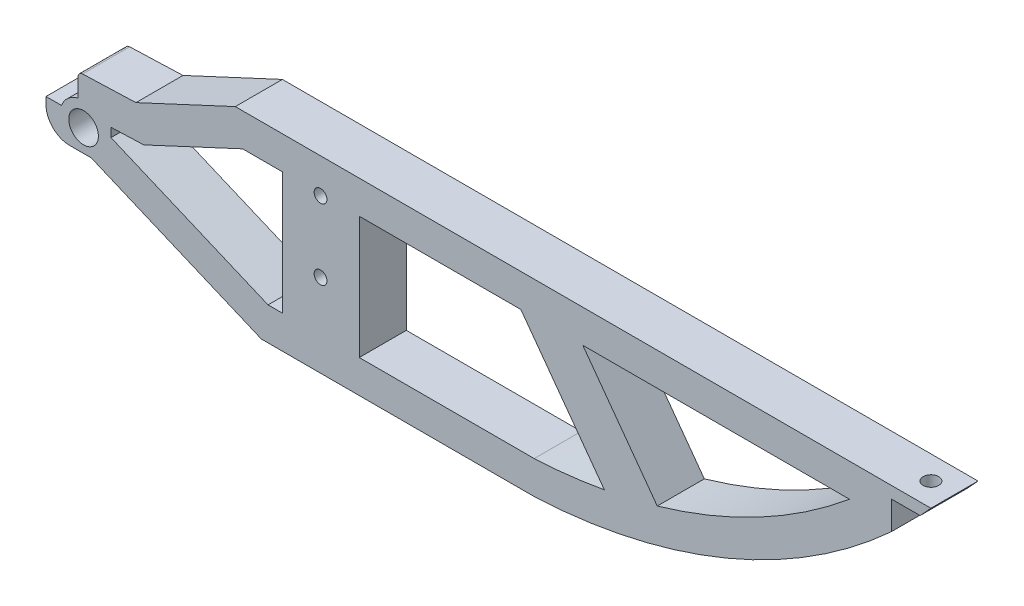
SolidWorks part; units mm, degrees
ref_plane "Front Plane" through (0, 0, 0) normal (0, 0, 1) x (1, 0, 0)
ref_plane "Top Plane" through (0, 0, 0) normal (0, 1, 0) x (1, 0, 0)
ref_plane "Right Plane" through (0, 0, 0) normal (1, 0, 0) x (0, 0, -1)
sketch "Sketch1" plane through (0, 0, 0) normal (0, 0, 1) x (1, 0, 0)
  line L1 (120.65, 25.4) -> (-120.65, 25.4)
  line L2 (120.65, 25.4) -> (120.65, -25.4)
  line L3 (120.65, -25.4) -> (-120.65, -25.4)
  line L4 (-120.65, 25.4) -> (-120.65, -25.4)
  line L5 (120.65, 25.4) -> (-120.65, -25.4) construction
  line L6 (120.65, -25.4) -> (-120.65, 25.4) construction
  point P0 (0, 0)
  dimension "D1" = 241.3
  dimension "D2" = 50.8
extrude "Boss-Extrude1" add sketch "Sketch1" along normal blind 12.7
sketch "Sketch3" plane through (0, 0, 12.7) normal (0, 0, 1) x (1, 0, 0)
  line L0 (0, 0) -> (-120.65, 0) construction
  line L1 (-120.65, 25.4) -> (-120.65, -25.4) construction
  circle A0 centre (-107.95, 0) radius 4
  dimension "D2" = 8
  dimension "D1" = 12.7
extrude "Cut-Extrude1" cut sketch "Sketch3" against normal through all
sketch "Sketch5" plane through (0, 0, 12.7) normal (0, 0, 1) x (1, 0, 0)
  line L0 (-120.65, -25.4) -> (120.65, -25.4) construction
  line L1 (-105.8942, -6.008) -> (-59.9903, -25.4)
  line L2 (-107.95, 6.35) -> (-67.0151, 25.4)
  line L3 (120.65, 25.4) -> (-120.65, 25.4) construction
  line L4 (-67.0151, 25.4) -> (-120.65, 25.4)
  line L5 (-120.65, 25.4) -> (-120.65, -25.4)
  line L6 (-120.65, -25.4) -> (-59.9903, -25.4)
  line L7 (120.65, 25.4) -> (120.65, -25.4)
  line L8 (120.65, -25.4) -> (0, -25.4)
  line L9 (-109.9582, -6.0241) -> (-105.8942, -6.008)
  line L10 (-118.0862, -6.0241) -> (-109.9582, -6.0241)
  line L11 (-118.0862, -6.0241) -> (-118.0862, 2.2309)
  line L12 (-118.0862, 2.2309) -> (-113.8952, 2.2309)
  arc A0 (0, -25.4) -> (120.65, 25.4) centre (6.9175, 126.8429) ccw
  arc A1 (-109.9582, -6.0241) -> (-105.8942, -6.008) centre (-107.95, 0) ccw construction
  arc A2 (-107.95, 6.35) -> (-113.8952, 2.2309) centre (-107.95, 0) ccw
  point P15 (-116.1445, -2.9908)
  line M3 (-120.65, 25.4) -> (-120.65, -25.4)
  line M4 (-120.65, -25.4) -> (120.65, -25.4)
  line M5 (120.65, -25.4) -> (120.65, 25.4)
  line M6 (120.65, 25.4) -> (-120.65, 25.4)
  dimension "D1" = 152.4
  dimension "D2" = 12.7
  dimension "D3" = 45.1505
  dimension "D4" = 45.9039
  dimension "D5" = 8.255
  dimension "D6" = 4.191
  dimension "D7" = 8.128
extrude "Cut-Extrude2" cut sketch "Sketch5" against normal through all contours A2 L2 L1 M6 M3 M4 | A0 L8 M5 region at (-83.2502, -16.4329, 12.7) region at (93.5193, -10.6939, 12.7)
sketch "Sketch6" plane through (0, 0, 12.7) normal (0, 0, 1) x (1, 0, 0)
  line L0 (-107.95, 0) -> (91.396, 0) construction
  arc A0 (13.8349, -25.4) -> (120.65, 25.4) centre (6.9175, 126.8429) ccw construction
  circle A1 centre (19.05, 0) radius 3.1347
  dimension "D1" = 127
sketch "Sketch7" plane through (0, 0, 0) normal (0, 0, -1) x (-1, 0, 0)
  line L0 (44.0204, -2.9977) -> (44.0204, 16.0523) construction
  point P3 (44.0204, -2.9977)
  point P4 (44.0204, 16.0523)
  dimension "D1" = 19.05
sketch "Sketch8" plane through (0, 0, 0) normal (0, 0, -1) x (-1, 0, 0)
  point P0 (44.0204, 16.0523)
  point P3 (44.0204, -2.9977)
hole_wizard "Tap Drill for #8-32 Tap1" positions "Sketch8" profile "Sketch9" hole size "#8-32" standard "ANSI Inch" end condition through all
sketch "Sketch9" plane through (-44.0204, 16.0523, 0) normal (1, 0, 0) x (0, 1, 0)
  line L0 (0, 0) -> (0, 12.7)
  line L1 (0, 12.7) -> (1.7272, 12.7)
  line L2 (1.7272, 12.7) -> (1.7272, 0)
  line L5 (1.7272, 0) -> (0, 0)
  line L11 (0, -6.35) -> (0, 107.95) construction
  dimension "Thru Hole Dia." = 3.4544
  dimension "Thru Hole Depth" = 12.7
ref_plane "Plane1" through (-114.3, 0, 0) normal (-1, 0, 0) x (0, 0, 1)
sketch "Sketch10" plane through (-114.3, 0, 0) normal (-1, 0, 0) x (0, 0, 1)
  line L0 (0, 0) -> (12.7, 0) construction
  line L1 (12.7, -3.1347) -> (12.7, 3.1347) construction
  circle A0 centre (6.0894, 0) radius 1.905
  dimension "D1" = 3.81
extrude "Cut-Extrude3" cut sketch "Sketch10" against normal blind 5.08
sketch "Sketch11" plane through (0, 0, 12.7) normal (0, 0, 1) x (1, 0, 0)
  line L0 (-93.8249, 12.9234) -> (-109.4459, 12.9234) construction
  line L1 (-107.95, 6.35) -> (-67.0151, 25.4) construction
  line L2 (-109.4459, 12.9234) -> (-109.4459, 5.6538) construction
  line L3 (-93.8249, 12.9234) -> (-109.4459, 5.6538)
  line L4 (-93.8249, 12.9234) -> (-109.4459, 12.3779)
  line L5 (-109.4459, 12.3779) -> (-109.4459, 5.6538)
  circle A1 centre (-107.95, 0) radius 4 construction
  dimension "D1" = 15.621
  dimension "D2" = 5.6538
  dimension "D3" = 178
extrude "Boss-Extrude2" add sketch "Sketch11" against normal up to surface (12.7 mm away) up to face at (-45.7476, 16.0523, 0)
sketch "Sketch12" plane through (0, 0, 12.7) normal (0, 0, 1) x (1, 0, 0)
  line L1 (10.0217, 16.51) -> (-33.5733, 16.51)
  line L24 (-33.5733, 16.51) -> (-33.5733, -16.51)
  line L25 (-54.2244, 16.51) -> (-54.2244, -16.51)
  line L26 (-54.2244, 16.51) -> (-65.0478, 16.51)
  line L27 (-33.5733, -16.51) -> (13.63, -16.51)
  line L28 (10.0217, 16.51) -> (32.5572, -14.3581)
  line L29 (26.7339, 16.51) -> (46.8231, -11.0072)
  line L30 (-100.5559, 3.793) -> (-100.5559, 1.3876)
  line L31 (-100.5559, 1.3876) -> (-58.1896, -16.51)
  line L32 (-58.1896, -16.51) -> (13.63, -16.51)
  line L33 (98.6876, 16.51) -> (-65.0478, 16.51)
  line L34 (-65.0478, 16.51) -> (-91.7106, 4.1018)
  line L35 (-91.7106, 4.1018) -> (-100.5559, 3.793)
  line L36 (-100.5559, 3.793) -> (-100.5559, 1.3876)
  line L37 (-100.5559, 1.3876) -> (-58.1896, -16.51)
  line L38 (-58.1896, -16.51) -> (-54.2244, -16.51)
  line L39 (98.6876, 16.51) -> (26.7339, 16.51)
  line L40 (-65.0478, 16.51) -> (-91.7106, 4.1018)
  line L41 (-91.7106, 4.1018) -> (-100.5559, 3.793)
  arc A0 (46.8231, -11.0072) -> (98.6876, 16.51) centre (6.9175, 126.8429) ccw
  arc A10 (13.63, -16.51) -> (98.6876, 16.51) centre (6.9175, 126.8429) ccw
  arc A11 (13.63, -16.51) -> (32.5572, -14.3581) centre (6.9175, 126.8429) ccw
  dimension "D1" = 8.89
extrude "Cut-Extrude4" cut sketch "Sketch12" against normal through all
sketch "Sketch13" plane through (0, 0, 12.7) normal (0, 0, 1) x (1, 0, 0)
  line L0 (-79.3724, -17.2121) -> (-87.4623, -19.4143)
  line L1 (-105.8942, -6.008) -> (-59.9903, -25.4) construction
  line L2 (-87.4623, -19.4143) -> (-89.1909, -13.0643)
  line L4 (-79.3724, -17.2121) -> (-89.1909, -13.0643)
  circle A0 centre (-107.95, 0) radius 4 construction
  dimension "D1" = 90
  dimension "D2" = 6.35
  dimension "D3" = 22.86
fillet "Fillet1" radius 6.35 1 edges at (-118.0862, -6.0241, 6.35)
sketch "Sketch14" plane through (0.0221, -5.5891, 0) normal (0.004, -1, 0) x (1, 0.004, 0)
  line L0 (-109.9812, 0) -> (-109.9812, 12.7) construction
  line L2 (-109.9812, 6.35) -> (-105.9171, 6.35) construction
  line L3 (-105.9171, 0) -> (-105.9171, 12.7) construction
  line L4 (-107.9492, 0) -> (-107.9492, 12.7) construction
  line L5 (-109.9812, 0) -> (-105.9171, 0) construction
  line L6 (-109.9812, 12.7) -> (-105.9171, 12.7) construction
  circle A0 centre (-107.9492, 6.35) radius 1.27
  dimension "D1" = 2.54
extrude "Cut-Extrude5" cut sketch "Sketch14" against normal blind 6.35
sketch "Sketch15" plane through (0, 0, 12.7) normal (0, 0, 1) x (1, 0, 0)
  line L0 (117.6404, 22.225) -> (110.0327, 22.225)
  line L1 (120.65, 22.225) -> (57.15, 22.225) construction
  line L2 (110.0327, 22.225) -> (110.0327, 12.8153)
  line L3 (110.0327, 12.8153) -> (117.6404, 12.8153)
  line L4 (117.6404, 12.8153) -> (117.6404, 22.225)
extrude "Cut-Extrude6" cut sketch "Sketch15" against normal through all
sketch "Sketch16" plane through (0, 0, 12.7) normal (0, 0, 1) x (1, 0, 0)
  line L0 (117.7449, 22.225) -> (117.6404, 22.225)
  line L1 (120.65, 22.225) -> (57.15, 22.225) construction
  line L2 (117.6404, 22.225) -> (117.6404, 22.0792)
  line L3 (117.6404, 22.0792) -> (117.7449, 22.0792)
  line L4 (117.7449, 22.0792) -> (117.7449, 22.225)
  dimension "D1" = 0.1046
  dimension "D2" = 0.1458
extrude "Cut-Extrude8" cut sketch "Sketch16" against normal through all contours L4 L0 L2 L3
sketch "Sketch18" plane through (0, 25.4, 0) normal (0, 1, 0) x (1, 0, 0)
  circle A0 centre (114.3, -6.35) radius 2.0828
extrude "Cut-Extrude9" cut sketch "Sketch18" against normal through all contours A0
fillet "Fillet2" radius 1.27 1 edges at (-109.4459, 12.3779, 6.35)
